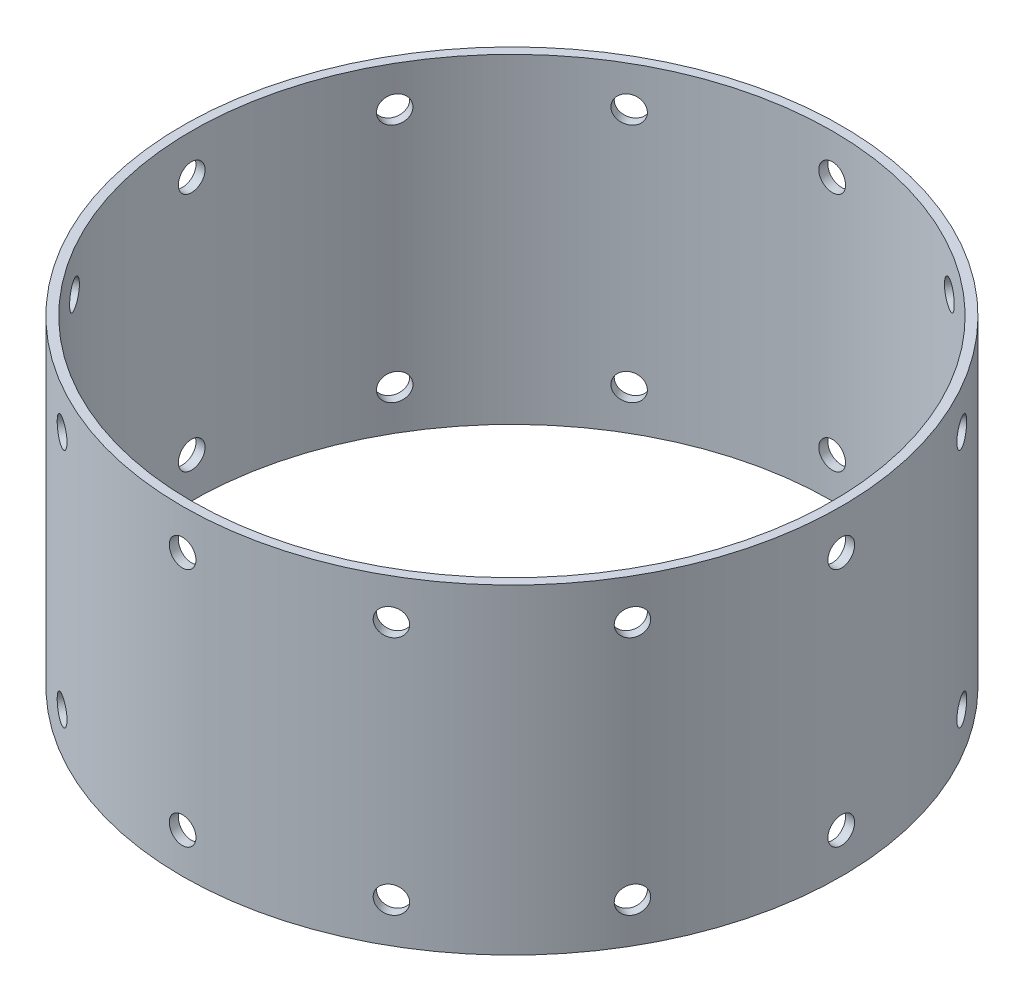
SolidWorks part; units mm, degrees
material "Fiberglass"
ref_plane "Front Plane" through (0, 0, 0) normal (0, 0, 1) x (1, 0, 0)
ref_plane "Top Plane" through (0, 0, 0) normal (0, 1, 0) x (1, 0, 0)
ref_plane "Right Plane" through (0, 0, 0) normal (1, 0, 0) x (0, 0, -1)
sketch "Sketch1" plane through (0, 0, 0) normal (0, 1, 0) x (1, 0, 0)
  circle A0 centre (0, 0) radius 76.2
  circle A1 centre (0, 0) radius 78.359
  dimension "D1" = 152.4
  dimension "D2" = 156.718
extrude "Boss-Extrude1" add sketch "Sketch1" along normal blind 76.2
sketch "Sketch2" plane through (0, 0, 0) normal (0, 0, 1) x (1, 0, 0)
  line L0 (0, 0) -> (0, 234.7266) construction
  line L1 (-76.2, 0) -> (76.2, 0) construction
  line L2 (-78.359, 0) -> (78.359, 0) construction
  line L3 (78.359, 38.1) -> (-54.7898, 38.1) construction
  line L4 (78.359, 0) -> (78.359, 76.2) construction
  circle A0 centre (0, 9.525) radius 3.175
  circle A1 centre (0, 66.675) radius 3.175
  dimension "D1" = 9.525
extrude "Cut-Extrude1" cut sketch "Sketch2" against normal through all
ref_axis "Axis1" through (0, 0, 0) along (0, 1, 0)
pattern_circular "CirPattern1" count 12 over 360 about axis through (0, 0, 0) along (0, 1, 0) of "Cut-Extrude1"
